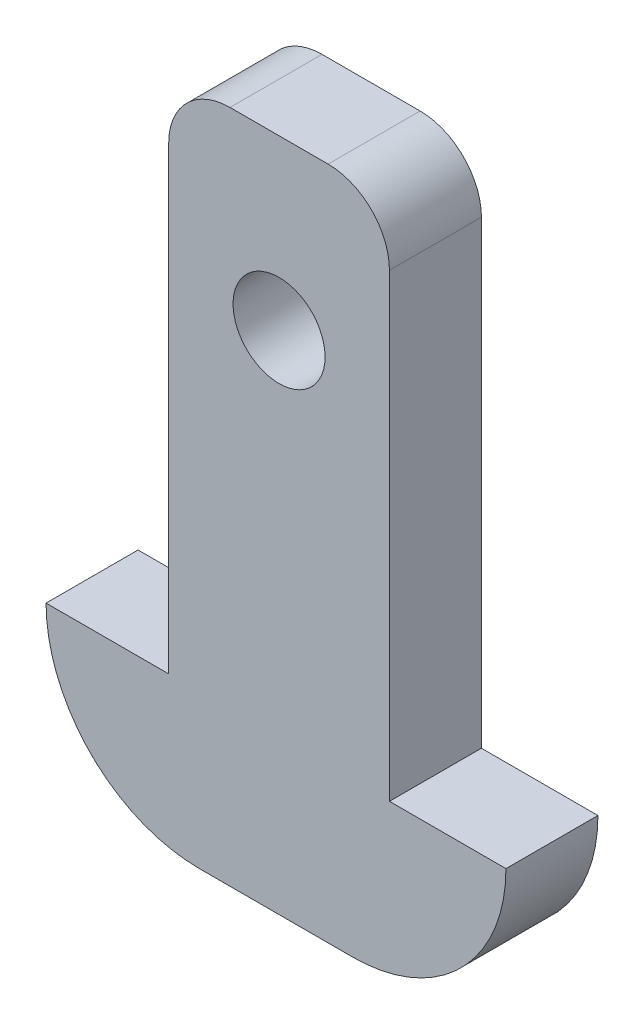
SolidWorks part; units mm, degrees
ref_plane "Plano frontal" through (0, 0, 0) normal (0, 0, 1) x (1, 0, 0)
ref_plane "Plano superior" through (0, 0, 0) normal (0, 1, 0) x (1, 0, 0)
ref_plane "Plano direito" through (0, 0, 0) normal (1, 0, 0) x (0, 0, -1)
sketch "Esboço1" plane through (0, 0, 0) normal (0, 0, 1) x (1, 0, 0)
  line L0 (0, 0) -> (4, 0)
  line L1 (4, 0) -> (4, 17)
  line L2 (4, 17) -> (11.2, 17)
  line L3 (11.2, 17) -> (11.2, 0)
  line L4 (11.2, 0) -> (15, 0)
  line L5 (15, 0) -> (15, -5)
  line L6 (15, -5) -> (0, -5)
  line L7 (0, -5) -> (0, 0)
  dimension "D1" = 5
  dimension "D2" = 7.2
  dimension "D3" = 15
  dimension "D4" = 4
  dimension "D5" = 17
extrude "Ressalto-extrusão1" add sketch "Esboço1" along normal blind 3
sketch "Esboço2" plane through (0, 0, 3) normal (0, 0, 1) x (1, 0, 0)
  line L0 (11.2, 17) -> (4, 17) construction
  line L1 (11.2, 0) -> (11.2, 17) construction
  circle A0 centre (7.6, 11.5) radius 1.5
  dimension "D1" = 3
  dimension "D3" = 3.6
  dimension "D2" = 5.5
extrude "Corte-extrusão1" cut sketch "Esboço2" against normal through all
fillet "Filete1" radius 5 2 edges at (0, -5, 1.5) (15, -5, 1.5)
fillet "Filete2" radius 2 2 edges at (4, 17, 1.5) (11.2, 17, 1.5)
